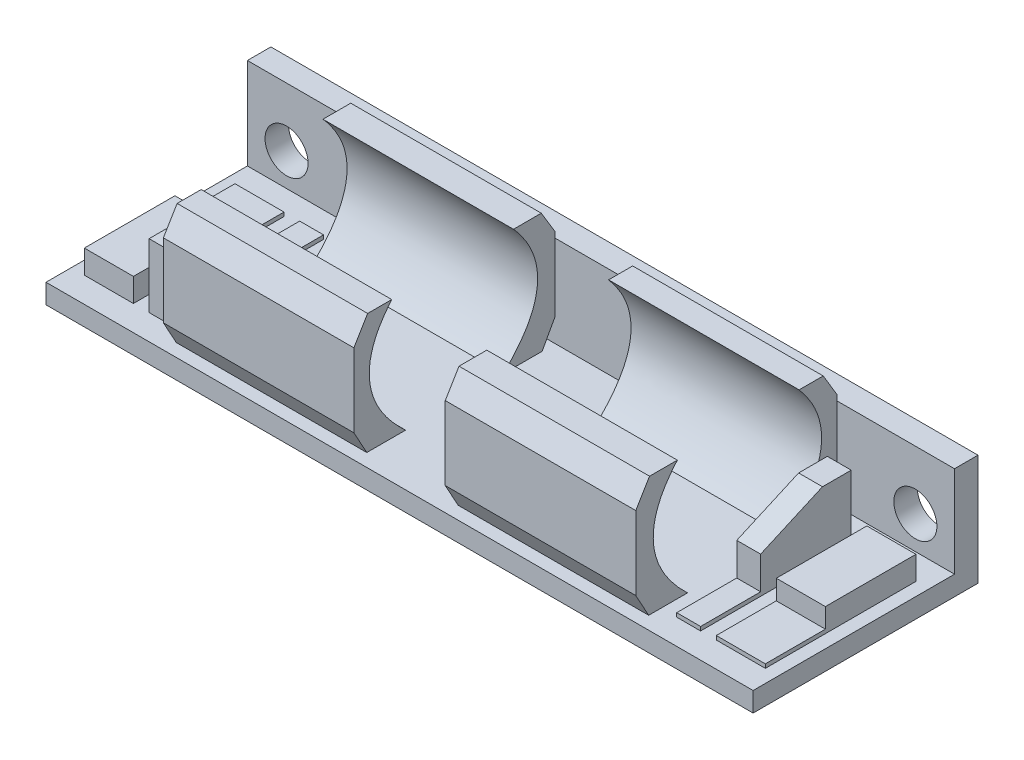
SolidWorks part; units mm, degrees
ref_plane "前视基准面" through (0, 0, 0) normal (0, 0, 1) x (1, 0, 0)
ref_plane "上视基准面" through (0, 0, 0) normal (0, 1, 0) x (1, 0, 0)
ref_plane "右视基准面" through (0, 0, 0) normal (1, 0, 0) x (0, 0, -1)
sketch "草图1" plane through (0, 0, 0) normal (0, 1, 0) x (1, 0, 0)
  line L0 (-2.643, 5.97) -> (-1.843, 5.97) construction
  line L1 (-2.643, -5.97) -> (-6.803, -5.97) construction
  line L2 (-2.643, -5.97) -> (-2.643, 5.97) construction
  line L3 (-2.643, 5.97) -> (-6.803, 5.97) construction
  line L4 (-6.803, -5.97) -> (-6.803, 5.97) construction
  line L5 (-2.643, -5.97) -> (-6.803, 5.97) construction
  line L6 (-2.643, 5.97) -> (-6.803, -5.97) construction
  line L7 (-1.843, 5.97) -> (-1.843, -5.97) construction
  line L8 (-1.843, -5.97) -> (-2.643, -5.97) construction
  line L9 (-1.843, 5.97) -> (0.387, 5.97) construction
  line L10 (0.387, 5.97) -> (0.387, -5.97) construction
  line L11 (0.387, -5.97) -> (-1.843, -5.97) construction
  line L12 (0.387, 5.97) -> (1.187, 5.97) construction
  line L13 (1.187, 5.97) -> (1.187, -5.97) construction
  line L14 (1.187, -5.97) -> (0.387, -5.97) construction
  line L15 (1.187, 5.97) -> (16.187, 5.97) construction
  line L16 (16.187, 5.97) -> (16.187, -5.97) construction
  line L17 (16.187, -5.97) -> (1.187, -5.97) construction
  line L18 (1.387, 6.17) -> (1.387, 3.45)
  line L19 (16.187, -3.25) -> (1.187, -3.25) construction
  line L20 (16.187, -3.25) -> (16.187, 3.25) construction
  line L21 (16.187, 3.25) -> (1.187, 3.25) construction
  line L22 (1.187, -3.25) -> (1.187, 3.25) construction
  line L23 (16.187, -3.25) -> (1.187, 3.25) construction
  line L24 (16.187, 3.25) -> (1.187, -3.25) construction
  line L25 (-2.843, -5.77) -> (-6.603, -5.77)
  line L26 (-2.843, -5.77) -> (-2.843, 5.77)
  line L27 (-2.843, 5.77) -> (-6.603, 5.77)
  line L28 (-6.603, -5.77) -> (-6.603, 5.77)
  line L29 (-2.843, -5.77) -> (-6.603, 5.77) construction
  line L30 (-2.843, 5.77) -> (-6.603, -5.77) construction
  line L31 (-1.643, -5.77) -> (0.187, -5.77)
  line L32 (-1.643, -5.77) -> (-1.643, 5.77)
  line L33 (-1.643, 5.77) -> (0.187, 5.77)
  line L34 (0.187, -5.77) -> (0.187, 5.77)
  line L35 (-1.643, -5.77) -> (0.187, 5.77) construction
  line L36 (-1.643, 5.77) -> (0.187, -5.77) construction
  line L37 (1.387, 3.45) -> (15.987, 3.45)
  line L38 (15.987, 3.45) -> (15.987, 6.17)
  line L39 (15.987, 6.17) -> (1.387, 6.17)
  line L40 (-13.1732, 0) -> (23.9155, 0) construction
  line L41 (15.987, -3.45) -> (15.987, -6.17)
  line L42 (15.987, -6.17) -> (1.387, -6.17)
  line L43 (1.387, -6.17) -> (1.387, -3.45)
  line L44 (1.387, -3.45) -> (15.987, -3.45)
  line L45 (15.987, 3.45) -> (15.987, -3.45)
  line L46 (1.387, 3.45) -> (1.387, -3.45)
  line L47 (1.387, 6.17) -> (-7.603, 6.17)
  line L48 (-7.603, 6.17) -> (-7.603, -6.17)
  line L49 (-7.603, -6.17) -> (1.387, -6.17)
  point P0 (-4.723, 0)
  point P5 (8.687, 0)
  point P19 (-4.723, 0)
  point P24 (-0.728, 0)
  dimension "D1" = 4.16
  dimension "D2" = 11.94
  dimension "D3" = 0.8
  dimension "D4" = 2.23
  dimension "D5" = 0.8
  dimension "D6" = 15
  dimension "D7" = 15
  dimension "D8" = 6.5
  dimension "D9" = 0.2
  dimension "D10" = 0.2
  dimension "D11" = 0.2
  dimension "D12" = 0.2
  dimension "D13" = 0.2
  dimension "D14" = 0.2
  dimension "D15" = 0.2
  dimension "D16" = 0.2
  dimension "D17" = 0.2
  dimension "D18" = 0.2
  dimension "D19" = 0.8
extrude "凸台-拉伸1" add sketch "草图1" against normal blind 1 contours L48 L49 L43 L46 L18 L47 L25 L28 L27 L26 L34 L31 L32 L33 | L44 L43 L42 L41 | L37 L46 L44 L45 | L38 L39 L18 L37 | L28 L25 L26 L27 | L31 L34 L33 L32 region at (8.687, 0, -4.81) region at (-2.6812, 0, 0) region at (8.687, 0, 0) region at (8.687, 0, 4.81) region at (-4.723, 0, 0) region at (-0.728, 0, 0)
extrude "凸台-拉伸2" add sketch "草图1<3>" along normal blind 10 contours L28 L25 L26 L27 | L31 L34 L33 L32 | L44 L43 L42 L41 | L38 L39 L18 L37 region at (8.687, 0, -4.81) region at (8.687, 0, 4.81) region at (-4.723, 0, 0) region at (-0.728, 0, 0)
sketch "草图1<3>" plane through (0, 0, 0) normal (0, 1, 0) x (1, 0, 0) same geometry as "草图1"
sketch "草图4" plane through (15.987, 0, 0) normal (1, 0, 0) x (0, 0, -1)
  line L0 (6.17, 10) -> (7.7076, 7.4436)
  line L1 (7.7076, 7.4436) -> (7.7076, 1.8053)
  line L2 (7.7076, 1.8053) -> (6.17, -1)
  line L3 (0, 2.2205) -> (0, -2.201) construction
  line L4 (-7.7076, 1.8053) -> (-6.17, -1)
  line L5 (-6.17, 10) -> (-7.7076, 7.4436)
  line L6 (-7.7076, 7.4436) -> (-7.7076, 1.8053)
  line L7 (-6.17, 10) -> (-6.17, -1)
  line L8 (6.17, 10) -> (6.17, -1)
extrude "凸台-拉伸3" add sketch "草图4" against normal blind 14.6
sketch "草图3" plane through (15.987, 0, 0) normal (1, 0, 0) x (0, 0, -1)
  line L0 (3.45, 0) -> (3.7432, 0)
  line L1 (3.45, 10) -> (3.5974, 10.1362)
  line L2 (6.17, 0) -> (6.17, 10) construction
  line L4 (3.45, 10) -> (3.45, 0)
  line L6 (-3.45, 0) -> (-3.7432, 0)
  line L7 (-3.45, 10) -> (-3.7432, 10.2945)
  line L8 (-3.45, 10) -> (-3.45, 0)
  spline S0 degree 2 poles (3.45, 0) (8.89, 5) (3.45, 10) knots 0 0 0 1 1 1 construction
  spline S1 degree 1 poles (3.5853, -0.1473) (3.5853, 10.1473) knots 0 0 1 1 construction
  spline S2 degree 3 poles (3.5853, -0.1473) (3.8077, 0.0571) (4.2497, 0.4898) (4.9947, 1.3335) (5.7235, 2.4028) (6.2513, 3.6955) (6.4294, 5) (6.2513, 6.3045) (5.7235, 7.5972) (4.9947, 8.6665) (4.2497, 9.5102) (3.8077, 9.9429) (3.5853, 10.1473) knots 0 0 0 0 0.0625 0.125 0.25 0.375 0.5 0.625 0.75 0.875 0.9375 1 1 1 1 only from (3.7432, 0) to (3.5974, 10.1362)
  spline S3 degree 3 poles (-3.7432, 0) (-3.782, 0.0356) (-3.8495, 0.0983) (-4.072, 0.309) (-4.4617, 0.6983) (-5.1526, 1.4807) (-5.8814, 2.5501) (-6.4092, 3.8428) (-6.5872, 5.1473) (-6.4092, 6.4517) (-5.8814, 7.7444) (-5.1526, 8.8138) (-4.4617, 9.5962) (-4.072, 9.9855) (-3.8494, 10.1962) (-3.782, 10.2589) (-3.7432, 10.2945) knots 0 0 0 0 0.010893 0.018156 0.0625 0.125 0.25 0.375 0.5 0.625 0.75 0.875 0.9375 0.98185 0.98911 1 1 1 1
  point P0 (6.17, 5)
  dimension "D1" = 0.2
extrude "切除-拉伸1" cut sketch "草图3" against normal blind 14.6
sketch "草图5" plane through (0.187, 0, 0) normal (1, 0, 0) x (0, 0, -1)
  line L0 (5.77, 10) -> (5.77, 0) construction
  line L1 (1.17, 2.8) -> (-3.5697, 4.9019)
  line L2 (-3.5697, 4.9019) -> (-5.77, 4.9019)
  line L3 (-3.5697, 0.3) -> (1.17, 0.3) construction
  line L4 (1.17, 10.4322) -> (1.17, 0.3) construction
  line L5 (-5.77, 0) -> (5.77, 0) construction
  line L6 (5.77, 0.3) -> (1.17, 0.3)
  line L7 (1.17, 2.8) -> (1.17, 0.3)
  line L8 (-5.77, 10) -> (-5.77, 0) construction
  line L9 (-5.77, 4.9019) -> (-5.77, 10)
  line L10 (-5.77, 10) -> (5.77, 10)
  line L11 (3.7431, 10) -> (6.17, 10) construction
  line L12 (5.77, 10) -> (5.77, 0.3)
  dimension "D1" = 4.6
  dimension "D2" = 0.3
  dimension "D3" = 2.5
extrude "切除-拉伸2" cut sketch "草图5" against normal blind 14.6
sketch "草图6" plane through (-2.843, 0, 0) normal (1, 0, 0) x (0, 0, -1)
  line L0 (1.17, 5.5386) -> (1.17, 1.8)
  line L1 (1.17, 2.8) -> (1.17, 0.3) construction
  line L2 (1.17, 1.8) -> (-3.7955, 1.8)
  line L3 (-3.7955, 1.8) -> (-5.77, 1.8)
  line L4 (-5.77, 4.9019) -> (-5.77, 0) construction
  line L5 (-5.77, 1.8) -> (-5.77, 5.5386)
  line L6 (-5.77, 5.5386) -> (1.17, 5.5386)
  line L7 (1.17, 0.3) -> (5.77, 0.3) construction
  dimension "D1" = 1.5
extrude "切除-拉伸3" cut sketch "草图6" against normal blind 14.6
ref_plane "基准面1" through (19.487, 0, 0) normal (1, 0, 0) x (0, 0, -1)
ref_plane "基准面2" through (0, 0, -12.7076) normal (0, 0, -1) x (-1, 0, 0)
ref_axis "基准轴1" through (19.487, -1.5501, 0) along (0, 1, 0)
pattern_circular "阵列(圆周)1" count 2 every 180 about axis through (19.487, -1.5501, 0) along (0, 1, 0) of bodies 111
sketch "草图7" plane through (1.387, 0, 0) normal (-1, 0, 0) x (0, 0, 1)
  line L1 (-10.4365, 12.0579) -> (10.2118, 12.0579)
  line L2 (-10.4365, 12.0579) -> (-10.4365, 9.1973)
  line L3 (-10.4365, 9.1973) -> (10.2118, 9.1973)
  line L4 (10.2118, 12.0579) -> (10.2118, 9.1973)
extrude "切除-拉伸4" cut sketch "草图7" against normal blind 38.6
sketch "草图8" plane through (0, 0, 0) normal (0, 1, 0) x (1, 0, 0)
  line L0 (-7.603, 6.17) -> (-7.603, -6.17) construction
  line L1 (46.577, -9.5243) -> (-7.603, -9.5243)
  line L2 (46.577, -9.5243) -> (46.577, 9.5243)
  line L3 (46.577, 9.5243) -> (-7.603, 9.5243)
  line L4 (-7.603, -9.5243) -> (-7.603, 9.5243)
  line L5 (46.577, -9.5243) -> (-7.603, 9.5243) construction
  line L6 (46.577, 9.5243) -> (-7.603, -9.5243) construction
  line L8 (22.987, -14.0243) -> (15.987, -14.0243)
  line L9 (22.987, -14.0243) -> (22.987, -9.5243)
  line L10 (22.987, -9.5243) -> (15.987, -9.5243)
  line L11 (15.987, -14.0243) -> (15.987, -9.5243)
  line L12 (22.987, -14.0243) -> (15.987, -9.5243) construction
  line L13 (22.987, -9.5243) -> (15.987, -14.0243) construction
  line L14 (9.2293, 0) -> (27.9561, 0) construction
  line L15 (15.987, 14.0243) -> (15.987, 9.5243)
  line L16 (22.987, 14.0243) -> (22.987, 9.5243)
  line L17 (22.987, 14.0243) -> (15.987, 14.0243)
  circle A0 centre (19.487, -11.7743) radius 1.6
  circle A1 centre (19.487, 11.7743) radius 1.6
  point P0 (19.487, 0)
  point P8 (19.487, -11.7743)
  dimension "D1" = 7
  dimension "D3" = 3.2
  dimension "D2" = 4.5
extrude "凸台-拉伸4" add sketch "草图8" against normal blind 1.5 contours L4 L1 L2 L3 | L11 L8 L9 L1 A0 | L16 L17 L15 L3 A1 region at (19.487, 0, 0) region at (22.9038, 0, 11.7743) region at (19.487, 0, -9.6075)
sketch "草图9" plane through (0, 0, 0) normal (0, 1, 0) x (1, 0, 0)
  line L0 (46.577, -9.5243) -> (46.577, 9.5243) construction
  line L1 (-7.603, 9.5243) -> (46.577, 9.5243)
  line L2 (-7.603, 9.5243) -> (-7.603, 7.7243)
  line L3 (-7.603, 7.7243) -> (46.577, 7.7243)
  line L4 (46.577, 9.5243) -> (46.577, 7.7243)
  dimension "D1" = 1.8
extrude "凸台-拉伸5" add sketch "草图9" along normal blind 7
sketch "草图10" plane through (0, 0, -7.7243) normal (0, 0, 1) x (1, 0, 0)
  line L0 (-2.843, 0) -> (-6.603, 0) construction
  line L1 (-7.603, 7) -> (-7.603, 0) construction
  line L2 (41.817, 0) -> (45.577, 0) construction
  line L3 (46.577, 7) -> (46.577, 0) construction
  circle A0 centre (-4.603, 2.5) radius 1.65
  circle A1 centre (43.577, 2.5) radius 1.65
  point P4 (-7.603, 3.5)
  dimension "D1" = 2.5
  dimension "D3" = 2.5
  dimension "D2" = 3
  dimension "D4" = 3
extrude "切除-拉伸5" cut sketch "草图10" against normal blind 5
extrude "凸台-拉伸6" add sketch "草图8<3>" along normal blind 2 contours L11 L8 L9 L1 A0 | L16 L17 L15 L3 A1 region at (22.9038, 0, 11.7743) region at (19.487, 0, -9.6075)
sketch "草图8<3>" plane through (0, 0, 0) normal (0, 1, 0) x (1, 0, 0) same geometry as "草图8"
sketch "草图11" plane through (0, 0, 0) normal (0, 1, 0) x (1, 0, 0)
  line L0 (-7.603, 7.7243) -> (-7.603, -9.5243) construction
  line L1 (-7.603, -7.7076) -> (46.577, -7.7076)
  line L2 (-7.603, -7.7076) -> (-7.603, -14.361)
  line L3 (-7.603, -14.361) -> (46.577, -14.361)
  line L4 (46.577, -7.7076) -> (46.577, -14.361)
  line L5 (46.577, -9.5243) -> (46.577, 7.7243) construction
  line L6 (37.587, -7.7076) -> (22.987, -7.7076) construction
extrude "切除-拉伸6" cut sketch "草图11" against normal mid plane 10
